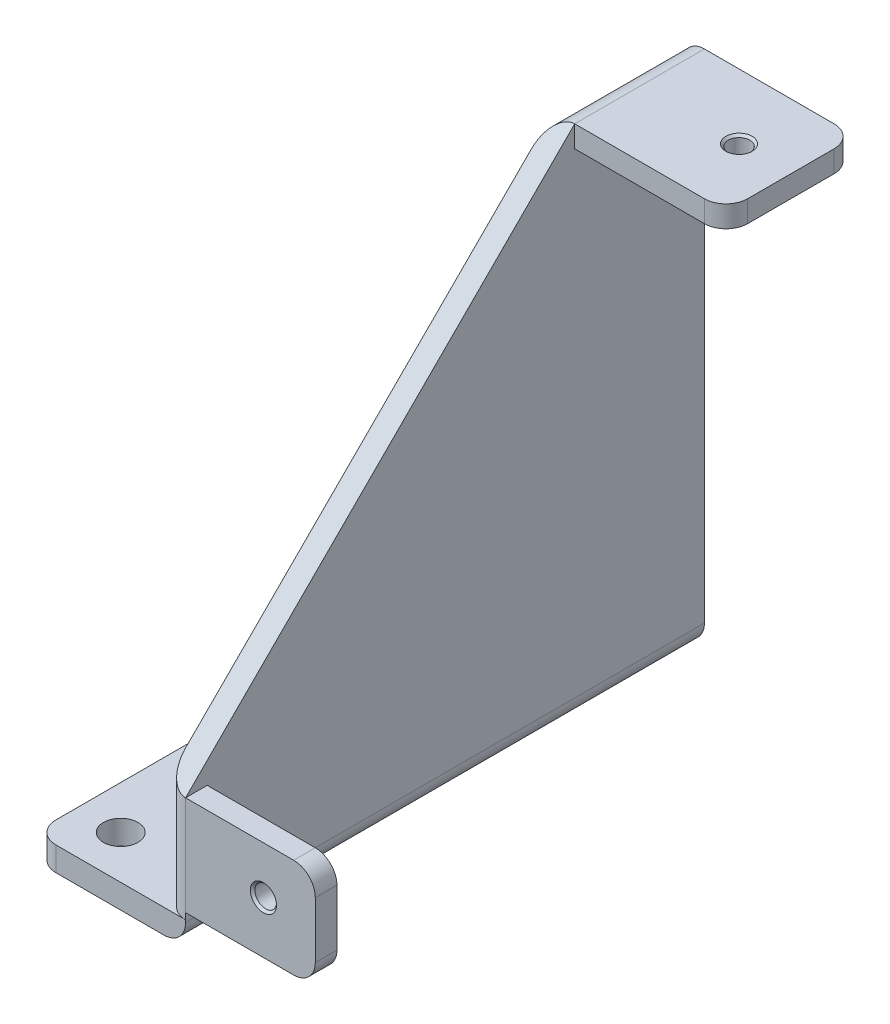
SolidWorks part; units mm, degrees
ref_plane "Piano frontale" through (0, 0, 0) normal (0, 0, 1) x (1, 0, 0)
ref_plane "Piano superiore" through (0, 0, 0) normal (0, 1, 0) x (1, 0, 0)
ref_plane "Piano destro" through (0, 0, 0) normal (1, 0, 0) x (0, 0, -1)
sketch "Schizzo1" plane through (0, 0, 0) normal (1, 0, 0) x (0, 0, -1)
  line L0 (0, 0) -> (120, 0)
  line L1 (120, 0) -> (120, 120)
  line L2 (120, 120) -> (90, 120)
  line L3 (90, 120) -> (0, 30)
  line L4 (0, 30) -> (0, 0)
  dimension "D1" = 120
  dimension "D2" = 120
  dimension "D3" = 30
  dimension "D4" = 30
extrude "Estrusione-Estrusione1" add sketch "Schizzo1" along normal blind 5
sketch "Schizzo2" plane through (0, 0, 0) normal (-1, 0, 0) x (0, 0, 1)
  line L0 (-120, 0) -> (-120, 120) construction
  line L1 (0, 0) -> (-120, 0)
  line L2 (0, 0) -> (0, 5.5713)
  line L3 (0, 5.5713) -> (-120, 5.5713)
  line L4 (-120, 0) -> (-120, 5.5713)
extrude "Estrusione-Estrusione2" add sketch "Schizzo2" along normal blind 30
sketch "Schizzo3" plane through (5, 0, 0) normal (1, 0, 0) x (0, 0, -1)
  line L1 (0, 7) -> (5, 7)
  line L2 (0, 7) -> (0, 30)
  line L3 (0, 30) -> (5, 30)
  line L4 (5, 7) -> (5, 30)
  dimension "D1" = 23
  dimension "D2" = 5
extrude "Estrusione-Estrusione3" add sketch "Schizzo3" along normal blind 30
sketch "Schizzo4" plane through (5, 0, 0) normal (1, 0, 0) x (0, 0, -1)
  line L0 (120, 0) -> (120, 120) construction
  line L1 (120, 120) -> (90, 120)
  line L2 (120, 120) -> (120, 115)
  line L3 (120, 115) -> (90, 115)
  line L4 (90, 120) -> (90, 115)
  dimension "D1" = 5
extrude "Estrusione-Estrusione4" add sketch "Schizzo4" along normal blind 35
fillet "Raccordo1" radius 5 9 edges at (40, 117.5, -120) (40, 117.5, -90) (35, 30, -2.5) (35, 7, -2.5) (-30, 2.7857, 0) (-30, 2.7857, -120) (5, 0, -60) (0, 120, -105)
hole_wizard "Foro filettato M6-2" positions "Schizzo8" profile "Schizzo7" tap size "M6" standard "ISO" end condition through all
sketch "Schizzo8" plane through (0, 120, 0) normal (0, 1, 0) x (1, 0, 0)
  line L0 (40, 115) -> (40, 95) construction
  line L1 (35, 120) -> (5, 120) construction
  point P0 (28, 105)
  dimension "D1" = 12
  dimension "D2" = 15
sketch "Schizzo7" plane through (28, 120, -105) normal (1, 0, 0) x (0, 0, 1)
  line L0 (0, 0) -> (0, 120)
  line L1 (0, 120) -> (2.5, 120)
  line L2 (2.5, 120) -> (2.5, 0.525)
  line L3 (2.5, 0.525) -> (3.025, 0)
  line L5 (3.025, 0) -> (0, 0)
  line L6 (-2.5, 0.525) -> (-3.025, 0) construction
  line L11 (0, -6.35) -> (0, 107.95) construction
  dimension "Thru Tap Drill Dia." = 5
  dimension "Thru Tap Drill Depth" = 120
  dimension "Near C'Sink Dia." = 6.05
  dimension "Near C'Sink Angle" = 90
cosmetic thread "Filettatura del foro3" parameters "D2"=6
hole_wizard "Foro filettato M6-3" positions "Schizzo12" profile "Schizzo11" tap size "M6" standard "ISO" end condition through all
sketch "Schizzo12" plane through (0, 0, 0) normal (0, 0, 1) x (1, 0, 0)
  line L0 (35, 25) -> (35, 12) construction
  line L1 (30, 7) -> (5, 7) construction
  point P0 (23, 19)
  dimension "D1" = 12
  dimension "D2" = 12
sketch "Schizzo11" plane through (23, 19, 0) normal (1, 0, 0) x (0, -1, 0)
  line L0 (0, 0) -> (0, 120.0001)
  line L1 (0, 120.0001) -> (2.5, 120.0001)
  line L2 (2.5, 120.0001) -> (2.5, 0.525)
  line L3 (2.5, 0.525) -> (3.025, 0)
  line L5 (3.025, 0) -> (0, 0)
  line L6 (-2.5, 0.525) -> (-3.025, 0) construction
  line L11 (0, -6.35) -> (0, 107.95) construction
  dimension "Thru Tap Drill Dia." = 5
  dimension "Thru Tap Drill Depth" = 120.0001
  dimension "Near C'Sink Dia." = 6.05
  dimension "Near C'Sink Angle" = 90
cosmetic thread "Filettatura del foro4" parameters "D2"=6
sketch "Schizzo13" plane through (0, 5.5713, 0) normal (0, 1, 0) x (1, 0, 0)
  line L0 (-25, 0) -> (5, 0) construction
  line L1 (-30, 5) -> (-30, 115) construction
  line L2 (-25, 120) -> (0, 120) construction
  circle A0 centre (-20, 110) radius 4
  circle A1 centre (-20, 10) radius 4
  dimension "D1" = 8
  dimension "D2" = 8
  dimension "D3" = 10
  dimension "D4" = 10
  dimension "D5" = 10
  dimension "D6" = 10
extrude "Taglio-Estrusione1" cut sketch "Schizzo13" against normal through all
